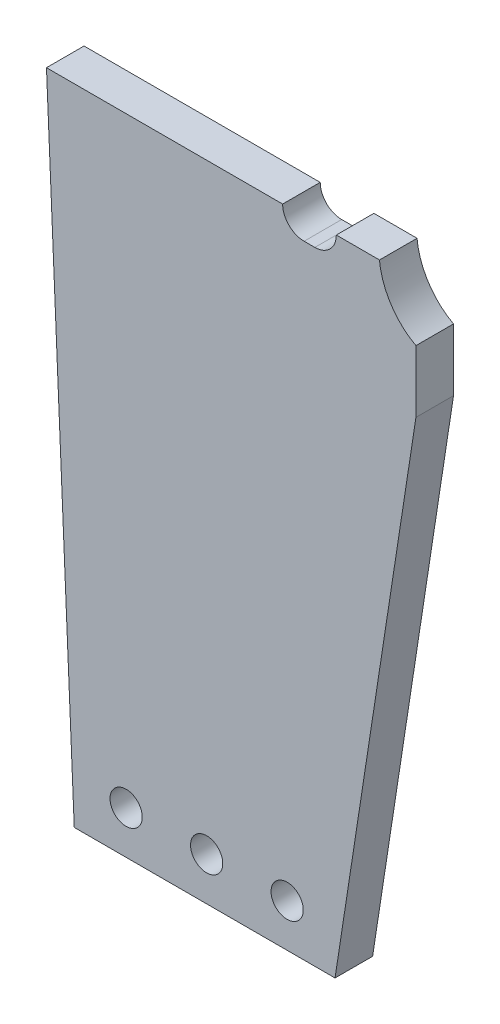
SolidWorks part; units mm, degrees
ref_plane "Front Plane" through (0, 0, 0) normal (0, 0, 1) x (1, 0, 0)
ref_plane "Top Plane" through (0, 0, 0) normal (0, 1, 0) x (1, 0, 0)
ref_plane "Right Plane" through (0, 0, 0) normal (1, 0, 0) x (0, 0, -1)
sketch "Sketch1" plane through (0, 0, 0) normal (0, 0, 1) x (1, 0, 0)
  line L0 (0, 20) -> (0, -305) construction
  line L1 (-22, -50) -> (22, -50)
  line L2 (-22, -50) -> (-11, -305)
  line L3 (-11, -305) -> (0, -305) construction
  line L4 (0, -305) -> (11, -305) construction
  line L5 (11, -305) -> (46.8389, -72)
  line L6 (46.8389, -72) -> (46.8389, -60.4217)
  line L7 (28, -54) -> (26, -54) construction
  line L8 (28, -54) -> (26, -54)
  line L9 (32, -50) -> (40.0462, -50)
  arc A0 (-11, -305) -> (11, -305) centre (0, -304.5255) ccw
  circle A1 centre (0, -305) radius 4.5
  arc A2 (28, -54) -> (32, -50) centre (28, -50) ccw construction
  arc A3 (22, -50) -> (26, -54) centre (26, -50) ccw construction
  arc A4 (28, -54) -> (32, -50) centre (28, -50) ccw
  arc A5 (22, -50) -> (26, -54) centre (26, -50) ccw
  spline S0 degree 3 poles (-413.0418, 1879.7645) (276.2189, -125.2168) (30.346, -91.1298) (48.299, -8.7941) (181.3198, -41.9405) (-1634.2989, 1047.346) knots -3.829034 -3.829034 -3.829034 -3.829034 0.434931 0.661678 4.201483 4.201483 4.201483 4.201483 only from (46.8389, -60.4217) to (46.8389, -34.5209) construction
  spline S1 degree 3 poles (46.8389, -60.4217) (42.9828, -58.3958) (38.9062, -51.8713) (41.1386, -41.633) (45.189, -37.4611) (46.8389, -34.5209) knots 0 0 0 0 0.434931 0.661678 0.998582 0.998582 0.998582 0.998582
  dimension "D2" = 9
  dimension "D3" = 11
  dimension "D1" = 325
extrude "Boss-Extrude1" add sketch "Sketch1" along normal blind 7 contours L6 S1 L1 L2 A0 L5 region at (7.91, -157.3608, 0)
sketch "Sketch2" plane through (0, 0, 7) normal (0, 0, 1) x (1, 0, 0)
  line L0 (-22, -50) -> (22, -50) construction
  line L1 (-156.4762, -170) -> (246.4423, -170)
  line L2 (-156.4762, -170) -> (-156.4762, -382.6459)
  line L3 (-156.4762, -382.6459) -> (246.4423, -382.6459)
  line L4 (246.4423, -170) -> (246.4423, -382.6459)
  dimension "D1" = 120
extrude "Cut-Extrude1" cut sketch "Sketch2" against normal blind 30
sketch "Sketch3" plane through (0, 0, 7) normal (0, 0, 1) x (1, 0, 0)
  line L0 (-17.1686, -162) -> (32.9955, -162) construction
  line L1 (-22, -50) -> (-16.8235, -170) construction
  line L2 (31.765, -170) -> (46.8389, -72) construction
  line L3 (31.765, -170) -> (-16.8235, -170) construction
  circle A0 centre (-7.1593, -162) radius 3
  circle A1 centre (7.8407, -162) radius 3
  circle A2 centre (22.8407, -162) radius 3
  dimension "D2" = 6
  dimension "D3" = 10
  dimension "D5" = 15
  dimension "D1" = 8
  dimension "D4" = 3
extrude "Cut-Extrude2" cut sketch "Sketch3" against normal through all
